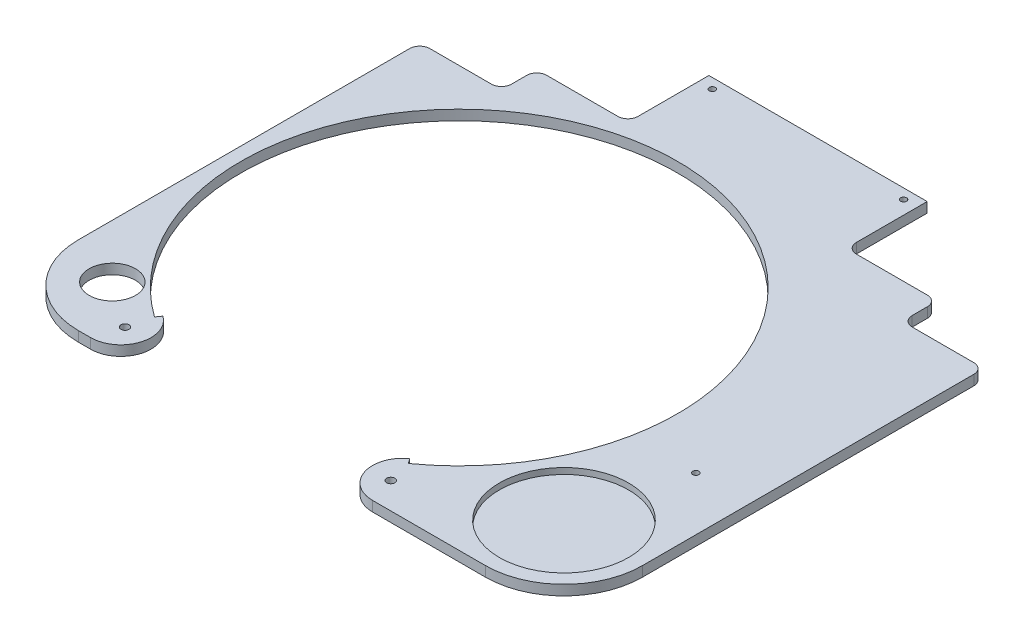
SolidWorks part; units mm, degrees
material "ABS PC"
ref_plane "Plan de face" through (0, 0, 0) normal (0, 0, 1) x (1, 0, 0)
ref_plane "Plan de dessus" through (0, 0, 0) normal (0, 1, 0) x (1, 0, 0)
ref_plane "Plan de droite" through (0, 0, 0) normal (1, 0, 0) x (0, 0, -1)
sketch "Esquisse1" plane through (0, 0, 0) normal (0, 1, 0) x (1, 0, 0)
  line L1 (-140.1, 31.2) -> (140.1, 31.2)
  line L2 (-140.1, 31.2) -> (-140.1, -245.0829)
  line L3 (-140.1, -245.0829) -> (140.1, -245.0829)
  line L4 (140.1, 31.2) -> (140.1, -245.0829)
  line L8 (-84, 31.2) -> (84, 31.2) construction
  line L9 (-140.1, 4) -> (-140.1, -4) construction
  line L10 (140.1, -4) -> (140.1, 4) construction
  line L11 (-95, -245.0829) -> (-100, -245.0829) construction
extrude "Boss.-Extru.1" add sketch "Esquisse1" along normal blind 5
sketch "Esquisse2" plane through (0, 5, 0) normal (0, 1, 0) x (1, 0, 0)
  line L0 (-86.2863, -217.8734) -> (-88.029, -220.3153) construction
  line L2 (-86.2863, -217.8734) -> (-88.029, -220.3153)
  line L3 (45, -245.0829) -> (-95, -245.0829)
  line L4 (36.2863, -217.8734) -> (38.029, -220.3153) construction
  line L5 (36.2863, -217.8734) -> (38.029, -220.3153)
  arc A1 (-95, -245.0829) -> (-86.2863, -217.8734) centre (-95, -230.0829) ccw construction
  arc A2 (-25, -23.5) -> (-88.029, -220.3153) centre (-25, -132) ccw construction
  arc A3 (-25, -23.5) -> (-88.029, -220.3153) centre (-25, -132) ccw
  arc A4 (-95, -245.0829) -> (-86.2863, -217.8734) centre (-95, -230.0829) ccw
  arc A5 (36.2863, -217.8734) -> (45, -245.0829) centre (45, -230.0829) ccw construction
  arc A6 (36.2863, -217.8734) -> (45, -245.0829) centre (45, -230.0829) ccw
  arc A7 (38.029, -220.3153) -> (-25, -23.5) centre (-25, -132) ccw
extrude "Enlèv. mat.-Extru.1" cut sketch "Esquisse2" against normal through all
sketch "Esquisse3" plane through (0, 5, 0) normal (0, 1, 0) x (1, 0, 0)
  arc A1 (89.8611, -236.1424) -> (112.3389, -176.0233) centre (101.1, -206.0829) ccw
  arc A2 (90.5615, -234.2691) -> (111.6385, -177.8967) centre (101.1, -206.0829) ccw
  arc A3 (90.5615, -234.2691) -> (111.6385, -177.8967) centre (101.1, -206.0829) ccw construction
  arc A4 (111.6385, -177.8967) -> (90.5615, -234.2691) centre (101.1, -206.0829) ccw
  arc A5 (111.6385, -177.8967) -> (90.5615, -234.2691) centre (101.1, -206.0829) ccw construction
  arc A6 (112.3389, -176.0233) -> (89.8611, -236.1424) centre (101.1, -206.0829) ccw
  dimension "D1" = 2
sketch "Esquisse4" plane through (0, 5, 0) normal (0, 1, 0) x (1, 0, 0)
  line L0 (140.1, -245.0829) -> (101.1, -245.0829)
  line L1 (140.1, -245.0829) -> (140.1, -206.0829)
  line L2 (-101.1, -245.0829) -> (-140.1, -245.0829)
  line L3 (-140.1, -245.0829) -> (-140.1, -206.0829)
  arc A0 (101.1, -245.0829) -> (140.1, -206.0829) centre (101.1, -206.0829) ccw construction
  arc A1 (101.1, -245.0829) -> (140.1, -206.0829) centre (101.1, -206.0829) ccw
  arc A2 (-140.1, -206.0829) -> (-101.1, -245.0829) centre (-101.1, -206.0829) ccw construction
  arc A3 (-140.1, -206.0829) -> (-101.1, -245.0829) centre (-101.1, -206.0829) ccw
extrude "Enlèv. mat.-Extru.3" cut sketch "Esquisse4" against normal through all
sketch "Esquisse5" plane through (0, 5, 0) normal (0, 1, 0) x (1, 0, 0)
  circle A0 centre (-91, -232) radius 2 construction
  circle A1 centre (-91, -232) radius 2
  circle A2 centre (41, -232) radius 2 construction
  circle A3 centre (41, -232) radius 2
extrude "Enlèv. mat.-Extru.4" cut sketch "Esquisse5" against normal through all
sketch "Esquisse6" plane through (0, 5, 0) normal (0, 1, 0) x (1, 0, 0)
  line L0 (99.5, 0) -> (99.5, 26.9) construction
  line L1 (140.1, 31.2) -> (0, 31.2)
  line L2 (140.1, 31.2) -> (140.1, -41.5125)
  line L3 (135.1, -36.5125) -> (104.5, -36.5125)
  line L4 (99.5, -24) -> (99.5, -31.5125)
  line L5 (94.5, -19) -> (59.2094, -19)
  line L6 (54.2094, -14) -> (54.2094, 21.2)
  line L7 (54.2094, 21.2) -> (-54.2094, 21.2)
  line L8 (-85, 21.2) -> (85, 21.2) construction
  line L9 (56.2094, 14) -> (56.2094, -14) construction
  line L10 (91.7094, -16) -> (92.7094, -16) construction
  line L11 (-54.2094, -14) -> (-54.2094, 21.2)
  line L12 (-94.5, -19) -> (-59.2094, -19)
  line L13 (-99.5, -24) -> (-99.5, -31.5125)
  line L14 (120.5, -36.5125) -> (130.66, -36.5125) construction
  line L15 (-135.1, -36.5125) -> (-104.5, -36.5125)
  line L16 (-140.1, 31.2) -> (-140.1, -41.5125)
  line L17 (-140.1, 31.2) -> (0, 31.2)
  line L25 (0, 0) -> (0, 86.4947) construction
  line L27 (140.1, 36.5125) -> (140.1, -245.0829) construction
  line L36 (140.1, 31.2) -> (-140.1, 31.2) construction
  arc A0 (140.1, -41.5125) -> (135.1, -36.5125) centre (135.1, -41.5125) ccw
  arc A1 (-99.5, -24) -> (-94.5, -19) centre (-94.5, -24) cw
  arc A2 (59.2094, -19) -> (54.2094, -14) centre (59.2094, -14) cw
  arc A3 (-104.5, -36.5125) -> (-99.5, -31.5125) centre (-104.5, -31.5125) ccw
  arc A4 (104.5, -36.5125) -> (99.5, -31.5125) centre (104.5, -31.5125) cw
  arc A5 (99.5, -24) -> (94.5, -19) centre (94.5, -24) ccw
  arc A6 (-59.2094, -19) -> (-54.2094, -14) centre (-59.2094, -14) ccw
  arc A7 (-140.1, -41.5125) -> (-135.1, -36.5125) centre (-135.1, -41.5125) cw
  point P41 (99.5, -36.5125)
  point P43 (99.5, -19)
  point P49 (0, 21.2)
  dimension "D1" = 5
  dimension "D2" = 2
  dimension "D3" = 3
extrude "Enlèv. mat.-Extru.5" cut sketch "Esquisse6" against normal through all
sketch "Esquisse7" plane through (0, 5, 0) normal (0, 1, 0) x (1, 0, 0)
  circle A0 centre (-113.5, -215.8) radius 11.5 construction
  circle A1 centre (-113.5, -215.8) radius 11.5
extrude "Enlèv. mat.-Extru.6" cut sketch "Esquisse7" against normal through all
extrude "Enlèv. mat.-Extru.7" cut sketch "Esquisse3" against normal blind 3
sketch "Esquisse8" plane through (0, 0, 0) normal (0, -1, 0) x (1, 0, 0)
  line L0 (108.5, 158) -> (118.5, 148) construction
  line L1 (-113.5, -21.2) -> (113.5, -21.2) construction
  line L2 (0, 0) -> (0, -63.4963) construction
  circle A0 centre (113.5, 153) radius 1.5
  circle A1 centre (47.5, -16.2) radius 1.5
  circle A2 centre (-47.5, -16.2) radius 1.5
  dimension "D1" = 3
  dimension "D4" = 3
  dimension "D2" = 5
  dimension "D3" = 95
extrude "Enlèv. mat.-Extru.8" cut sketch "Esquisse8" against normal through all
